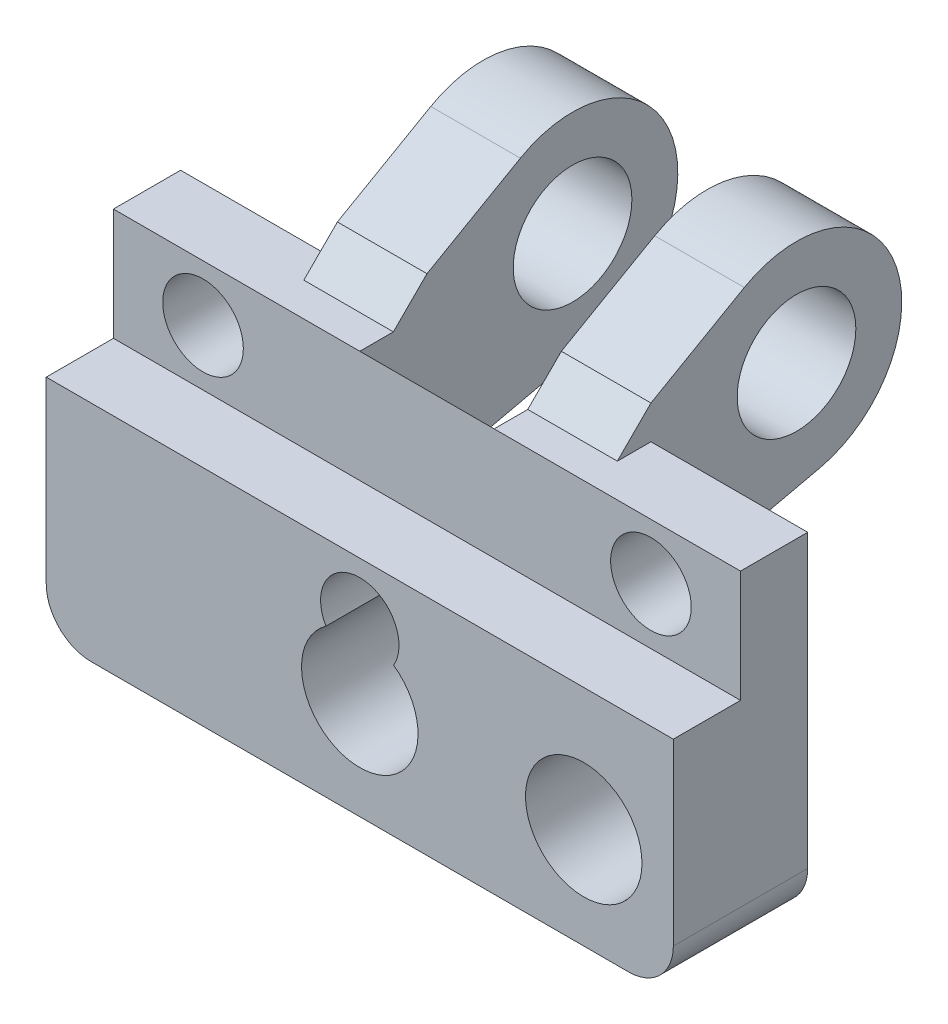
SolidWorks part; units mm, degrees
ref_plane "Front Plane" through (0, 0, 0) normal (0, 0, 1) x (1, 0, 0)
ref_plane "Top Plane" through (0, 0, 0) normal (0, 1, 0) x (1, 0, 0)
ref_plane "Right Plane" through (0, 0, 0) normal (1, 0, 0) x (0, 0, -1)
sketch "Sketch1" plane through (0, 0, 0) normal (0, 0, 1) x (1, 0, 0)
  line L1 (-14, -2.5) -> (14, -2.5)
  line L2 (-14, -2.5) -> (-14, 2.5)
  line L3 (-14, 2.5) -> (14, 2.5)
  line L4 (14, -2.5) -> (14, 2.5)
  line L5 (-14, -2.5) -> (14, 2.5) construction
  line L6 (-14, 2.5) -> (14, -2.5) construction
  line L7 (14, -2.5) -> (-14, -2.5)
  line L8 (14, -2.5) -> (14, -12.5)
  line L9 (14, -12.5) -> (-14, -12.5)
  line L10 (-14, -2.5) -> (-14, -12.5)
  point P0 (0, 0)
  dimension "D1" = 5
  dimension "D2" = 28
  dimension "D3" = 10
extrude "Boss-Extrude1" add sketch "Sketch1" along normal blind 3 contours L1 L4 L3 L2 region at (0, 0, 0)
extrude "Boss-Extrude2" add sketch "Sketch1<3>" along normal blind 6 contours L1 L10 L9 L8 region at (0, -7.5, 0)
sketch "Sketch1<3>" plane through (0, 0, 0) normal (0, 0, 1) x (1, 0, 0) same geometry as "Sketch1"
sketch "Sketch2" plane through (0, 0, 3) normal (0, 0, 1) x (1, 0, 0)
  line L0 (0, 0) -> (0, 5.0755) construction
  line L1 (14, -2.5) -> (14, 2.5) construction
  circle A0 centre (10, 0) radius 1.8
  circle A1 centre (-10, 0) radius 1.8
  point P7 (0, 0)
  point P8 (0, 0)
  dimension "D1" = 3.6
  dimension "D2" = 4
extrude "Cut-Extrude1" cut sketch "Sketch2" against normal through all
sketch "Sketch3" plane through (0, 0, 6) normal (0, 0, 1) x (1, 0, 0)
  line L0 (0, 0) -> (0, -8.2766) construction
  line L3 (14, -12.5) -> (-14, -12.5) construction
  line L4 (14, -2.5) -> (14, -12.5) construction
  circle A0 centre (10, -8) radius 2.6
  circle A1 centre (0, -8) radius 2.6
  point P7 (0, 0)
  point P10 (0.9829, -8)
  dimension "D2" = 5.2
  dimension "D1" = 4
  dimension "D3" = 8
  dimension "D4" = 10
  dimension "D5" = 4.5
extrude "Cut-Extrude2" cut sketch "Sketch3" against normal through all
sketch "Sketch4" plane through (0, 0, 0) normal (0, 0, -1) x (-1, 0, 0)
  circle A0 centre (0, -5) radius 1.75
  point P2 (0, 0)
  dimension "D1" = 3.5
  dimension "D2" = 5
extrude "Cut-Extrude3" cut sketch "Sketch4" against normal through all
sketch "Sketch5" plane through (0, 0, 0) normal (1, 0, 0) x (0, 0, -1)
  line L1 (0, -12.5) -> (0, 2.5) construction
  line L2 (0, 4) -> (0, -4)
  line L4 (0, 4) -> (4.1689, 6.3812)
  line L5 (7.5433, -2.2827) -> (0, -4)
  line L6 (-3, 2.5) -> (0, 2.5) construction
  arc A2 (4.1689, 6.3812) -> (7.5433, -2.2827) centre (6.5, 2.3) cw
  circle A3 centre (6.5, 2.3) radius 2.65
  dimension "D1" = 5.3
  dimension "D2" = 4.7
  dimension "D3" = 8
  dimension "D4" = 1.5
  dimension "D5" = 6.5
  dimension "D6" = 2.3
extrude "Boss-Extrude3" add sketch "Sketch5" along normal mid plane 14
extrude "Cut-Extrude5" cut sketch "Sketch5<3>" against normal mid plane 6
sketch "Sketch5<3>" plane through (0, 0, 0) normal (1, 0, 0) x (0, 0, -1) same geometry as "Sketch5"
chamfer "Chamfer1" distance 3 angle 45 1 edges at (0, 2.5, 0)
chamfer "Chamfer2" distance 1.5 angle 45 2 edges at (-5, 2.5, 0) (5, 2.5, 0)
fillet "Fillet1" radius 2 4 edges at (-5, -4, 0) (5, -4, 0) (-14, -12.5, 3) (14, -12.5, 3)
